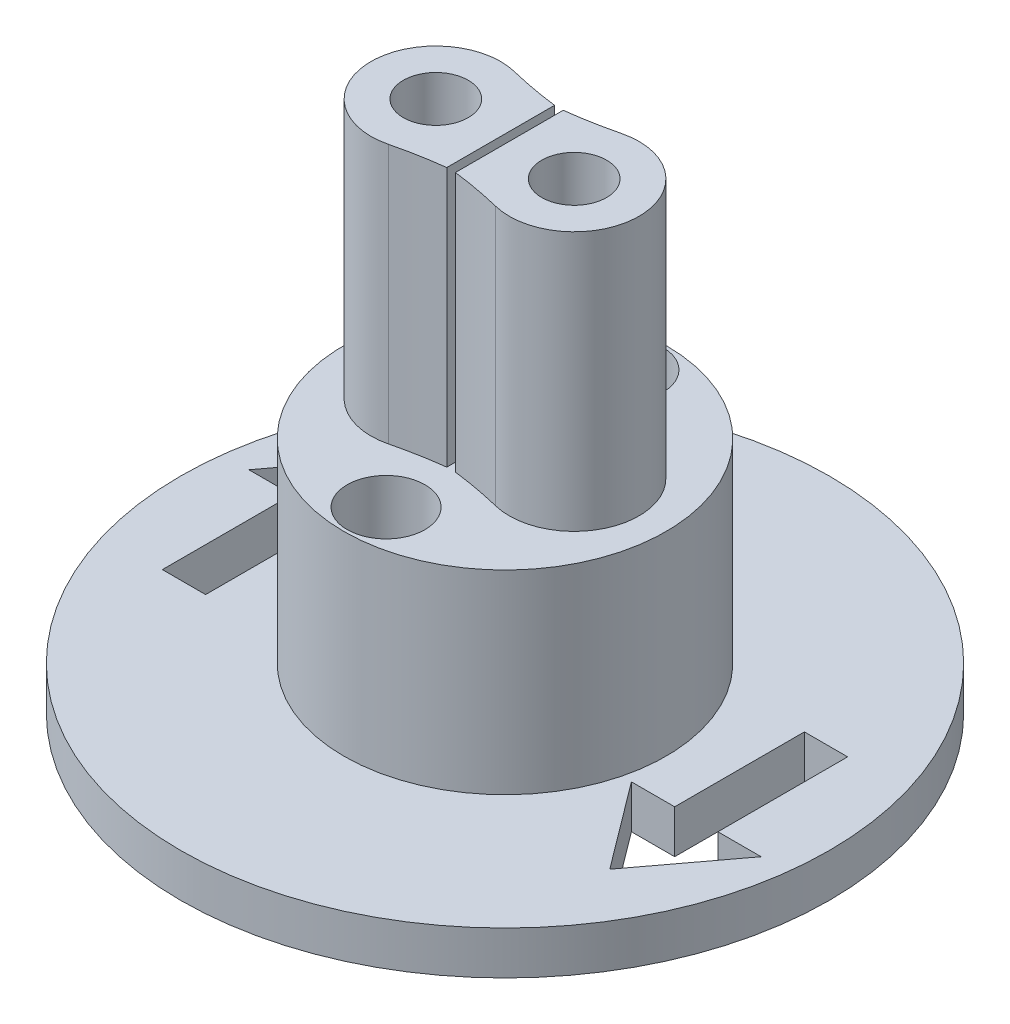
SolidWorks part; units mm, degrees
ref_plane "Front Plane" through (0, 0, 0) normal (0, 0, 1) x (1, 0, 0)
ref_plane "Top Plane" through (0, 0, 0) normal (0, 1, 0) x (1, 0, 0)
ref_plane "Right Plane" through (0, 0, 0) normal (1, 0, 0) x (0, 0, -1)
sketch "Sketch1" plane through (0, 0, 0) normal (0, 1, 0) x (1, 0, 0)
  circle A0 centre (0, 0) radius 9.4615
  dimension "D1" = 18.923
extrude "Boss-Extrude1" add sketch "Sketch1" along normal blind 13.97
sketch "Sketch2" plane through (0, 13.97, 0) normal (0, 1, 0) x (1, 0, 0)
  circle A0 centre (-4.064, 0) radius 1.905
  circle A1 centre (4.064, 0) radius 1.905
  dimension "D1" = 3.81
extrude "Cut-Extrude1" cut sketch "Sketch2" against normal through all
sketch "Sketch4" plane through (0, 13.97, 0) normal (0, 1, 0) x (1, 0, 0)
  line L0 (-0.254, 9.4581) -> (-0.254, -9.4581)
  line L1 (0, 0) -> (0, 9.4615) construction
  line L2 (0.254, 9.4581) -> (0.254, -9.4581)
  circle A0 centre (0, 0) radius 9.4615 construction
  arc A1 (-1.4863, -2.8056) -> (1.4863, -2.8056) centre (0, 0) ccw
  arc A2 (-1.4863, 2.8056) -> (-1.4863, -2.8056) centre (-4.064, 0) ccw
  arc A3 (1.4863, -2.8056) -> (1.4863, 2.8056) centre (4.064, 0) ccw
  arc A6 (1.4863, 2.8056) -> (-1.4863, 2.8056) centre (0, 0) ccw
  circle M4 centre (-4.064, 0) radius 1.905
  circle M5 centre (4.064, 0) radius 1.905
  dimension "D2" = 6.35
  dimension "D3" = 7.62
  dimension "D1" = 0.508
extrude "Boss-Extrude2" add sketch "Sketch4" along normal blind 15.24 contours L0 A6 A2 A1 M4 | A3 A6 L2 A1 M5 region at (-0.3618, 13.97, 0) region at (0.8583, 13.97, -2.9447)
fillet "Fillet1" radius 25.4 4 edges at (1.4863, 21.59, -2.8056) (-1.4863, 21.59, -2.8056) (1.4863, 21.59, 2.8056) (-1.4863, 21.59, 2.8056)
sketch "Sketch5" plane through (0, 0, 0) normal (0, -1, 0) x (1, 0, 0)
  line L0 (0, 0) -> (9.4615, 0) construction
  circle A0 centre (0, 6.985) radius 2.286
  circle A1 centre (0, 0) radius 9.4615 construction
  circle A2 centre (0, -6.985) radius 2.286
  dimension "D2" = 4.572
  dimension "D1" = 6.985
extrude "Cut-Extrude2" cut sketch "Sketch5" against normal through all
sketch "Sketch6" plane through (0, 0, 0) normal (0, -1, 0) x (1, 0, 0)
  circle A0 centre (0, 0) radius 9.4615
  circle A1 centre (0, 0) radius 19.05
  circle A2 centre (0, 0) radius 9.4615 construction
  dimension "D1" = 38.1
extrude "Boss-Extrude3" add sketch "Sketch6" against normal offset from surface (2.54 mm away) 11.43 up to face at (0, 13.97, 9.271)
sketch "Sketch7" plane through (0, 0, 0) normal (0, -1, 0) x (1, 0, 0)
  line L0 (12.2842, 2.3196) -> (9.7442, 2.3196)
  line L1 (12.2842, -5.3004) -> (14.8242, -5.3004)
  line L2 (12.2842, -5.3004) -> (12.2842, 2.3196)
  line L3 (12.2842, 2.3196) -> (14.8242, 2.3196)
  line L4 (14.8242, -5.3004) -> (14.8242, 2.3196)
  line L5 (9.7442, 2.3196) -> (13.5542, 7.3996)
  line L6 (13.5542, 7.3996) -> (17.3642, 2.3196)
  line L7 (17.3642, 2.3196) -> (14.8242, 2.3196)
  point P6 (13.5542, 2.3196)
  point P8 (0, 0)
  point P9 (14.1683, -5.0884)
  point P10 (17.3642, 2.3196)
  dimension "D1" = 2.54
  dimension "D2" = 7.62
  dimension "D3" = 5.08
extrude "Cut-Extrude3" cut sketch "Sketch7" against normal through all contours L1 L4 L3 L2 | L7 L6 L5 L0 L3 region at (13.5542, 0, -1.4904) region at (13.5542, 0, 4.013)
pattern_circular "CirPattern1" count 2 over 360 about axis through (0, 67.8515, 0) along (0, -1, 0) of "Cut-Extrude3" reverse direction yes
